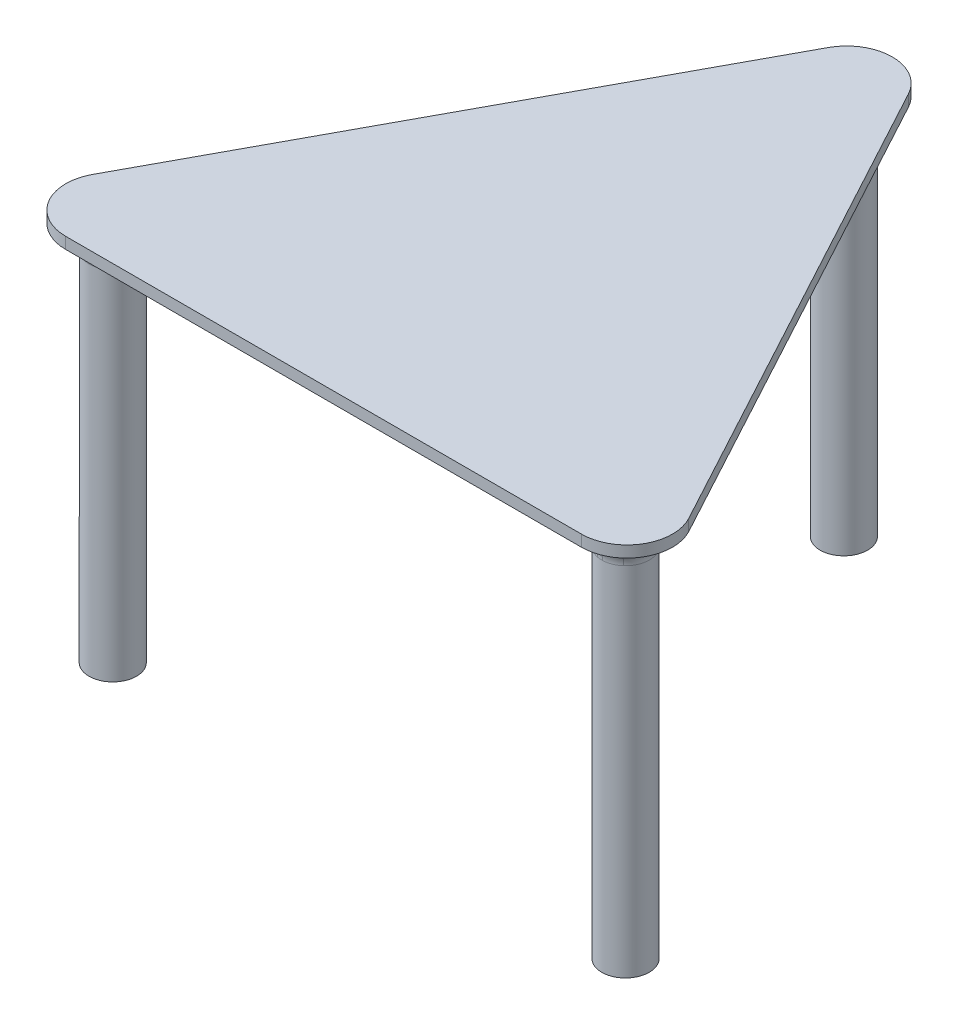
SolidWorks part; units mm, degrees
ref_plane "Front Plane" through (0, 0, 0) normal (0, 0, 1) x (1, 0, 0)
ref_plane "Top Plane" through (0, 0, 0) normal (0, 1, 0) x (1, 0, 0)
ref_plane "Right Plane" through (0, 0, 0) normal (1, 0, 0) x (0, 0, -1)
sketch "Sketch1" plane through (0, 0, 0) normal (0, 1, 0) x (1, 0, 0)
  line L0 (-45.1615, 35.4007) -> (-72.3152, -14.8954)
  line L1 (-68.0915, -21.9757) -> (-13.784, -21.9757)
  line L2 (-9.5602, -14.8954) -> (-36.714, 35.4007)
  circle A0 centre (-13.9377, -17.1757) radius 1
  circle A1 centre (-67.9377, -17.1757) radius 1
  circle A2 centre (-40.9377, 32.8243) radius 1
  circle A3 centre (-13.9377, -17.1757) radius 2.5
  circle A4 centre (-67.9377, -17.1757) radius 2.5
  circle A5 centre (-40.9377, 32.8243) radius 2.5
  arc A6 (-36.714, 35.4007) -> (-45.1615, 35.4007) centre (-40.9377, 33.1204) ccw
  arc A7 (-68.0915, -21.9757) -> (-72.3152, -14.8954) centre (-68.0915, -17.1757) cw
  arc A8 (-13.784, -21.9757) -> (-9.5602, -14.8954) centre (-13.784, -17.1757) ccw
  point P8 (-40.9377, -21.9757)
  point P18 (-40.9377, 43.2243)
  point P21 (-76.1377, -21.9757)
  point P24 (-5.7377, -21.9757)
  dimension "D1" = 2
  dimension "D2" = 5
  dimension "D3" = 2
  dimension "D4" = 5
  dimension "D5" = 2
  dimension "D6" = 5
  dimension "D13" = 4.8
  dimension "D14" = 4.8
  dimension "D15" = 4.8
  dimension "D7" = 50
  dimension "D8" = 27
  dimension "D9" = 27
  dimension "D10" = 70.4
  dimension "D11" = 65.2
  dimension "D12" = 10.4
extrude "Boss-Extrude1" add sketch "Sketch1" along normal blind 1.2 contours L1 A8 L2 A6 L0 A7 A3 A4 A5 | A5 A2 | A2 | A3 A0 | A0 | A4 A1 | A1 region at (-40.9377, 0, 0.2878) region at (-13.9377, 0, 17.1757) region at (-67.9377, 0, 17.1757) region at (-40.9377, 0, -32.8243) region at (-16.367, 0, 17.1757) region at (-70.367, 0, 17.1757) region at (-43.367, 0, -32.8243)
extrude "Boss-Extrude2" add sketch "Sketch1<3>" against normal blind 40 contours A5 A2 | A4 A1 | A3 A0 region at (-16.367, 0, 17.1757) region at (-70.367, 0, 17.1757) region at (-43.367, 0, -32.8243)
sketch "Sketch1<3>" plane through (0, 0, 0) normal (0, 1, 0) x (1, 0, 0) same geometry as "Sketch1"
sketch "Sketch2" plane through (0, 0, 0) normal (0, -1, 0) x (1, 0, 0)
  line L0 (-17.6019, 0) -> (-64.2735, 0) construction
  line L1 (-9.5602, 14.8954) -> (-36.714, -35.4007) construction
  line L2 (-45.1615, -35.4007) -> (-72.3152, 14.8954) construction
  text T0 "GPS\r\nthis side down"
extrude "Boss-Extrude3" add sketch "Sketch2" along normal blind 1
fillet "Fillet1" radius 2.4 3 edges at (-67.9377, 0, 19.6757) (-13.9377, 0, 19.6757) (-40.9377, 0, -30.3243)
